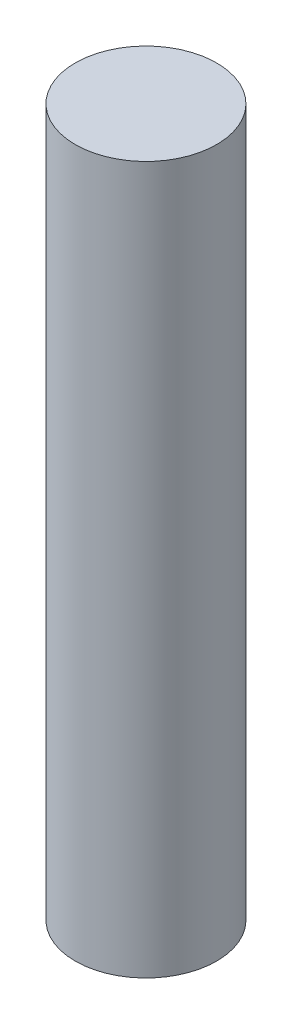
SolidWorks part; units mm, degrees
material "环氧树脂,未充填"
ref_plane "前视基准面" through (0, 0, 0) normal (0, 0, 1) x (1, 0, 0)
ref_plane "上视基准面" through (0, 0, 0) normal (0, 1, 0) x (1, 0, 0)
ref_plane "右视基准面" through (0, 0, 0) normal (1, 0, 0) x (0, 0, -1)
sketch "Sketch1" plane through (0, 0, 0) normal (0, 1, 0) x (1, 0, 0)
  circle A0 centre (0, 0) radius 3.5
  dimension "D1" = 7
extrude "Boss-Extrude1" add sketch "Sketch1" along normal blind 35
